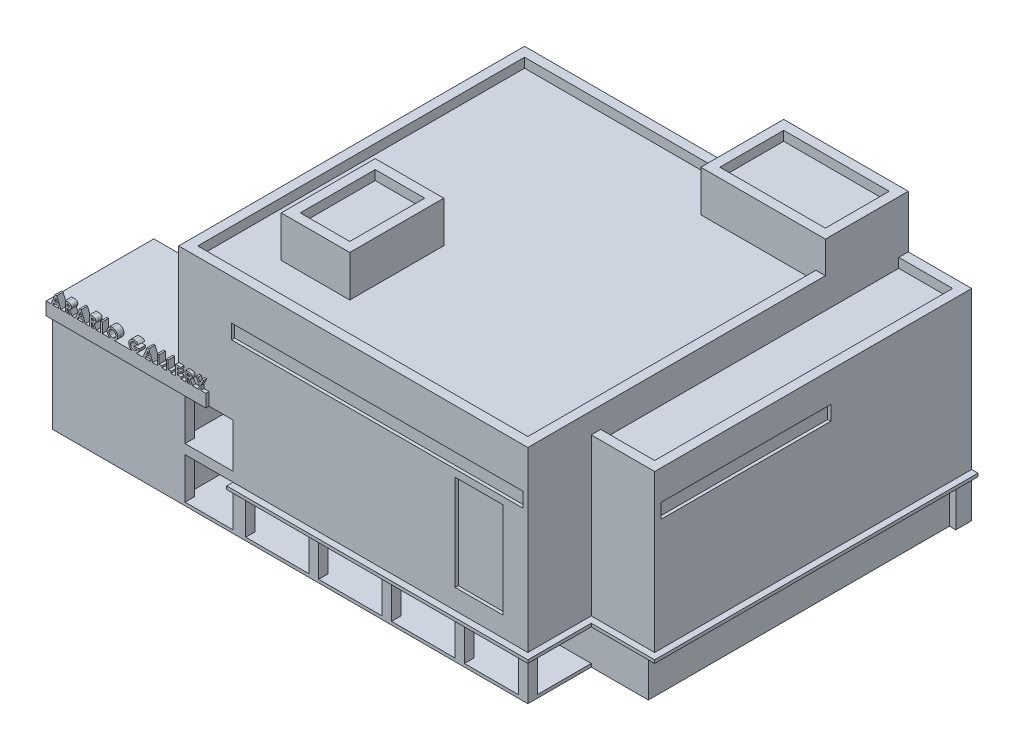
SolidWorks part; units mm, degrees
ref_plane "Front Plane" through (0, 0, 0) normal (0, 0, 1) x (1, 0, 0)
ref_plane "Top Plane" through (0, 0, 0) normal (0, 1, 0) x (1, 0, 0)
ref_plane "Right Plane" through (0, 0, 0) normal (1, 0, 0) x (0, 0, -1)
sketch "Sketch1" plane through (0, 0, 0) normal (0, 0, 1) x (1, 0, 0)
  line L1 (0, 0) -> (170, 0)
  line L2 (0, 0) -> (0, 70)
  line L3 (0, 70) -> (170, 70)
  line L4 (170, 0) -> (170, 70)
  dimension "D1" = 170
  dimension "D2" = 70
extrude "Boss-Extrude1" add sketch "Sketch1" along normal blind 120
sketch "Sketch2" plane through (0, 0, 120) normal (0, 0, 1) x (1, 0, 0)
  line L0 (0, 70) -> (0, 0) construction
  line L1 (0, 70) -> (39.861, 70)
  line L2 (0, 70) -> (0, 35)
  line L3 (0, 35) -> (39.861, 35)
  line L4 (39.861, 70) -> (39.861, 35)
  point P8 (0, 35)
extrude "Cut-Extrude1" cut sketch "Sketch2" against normal blind 150
sketch "Sketch3" plane through (0, 0, 0) normal (-1, 0, 0) x (0, 0, 1)
  line L0 (0, 35) -> (120, 35) construction
  line L1 (0, 0) -> (88.3399, 0)
  line L2 (0, 0) -> (0, 35)
  line L3 (0, 35) -> (88.3399, 35)
  line L4 (88.3399, 0) -> (88.3399, 35)
extrude "Cut-Extrude2" cut sketch "Sketch3" against normal up to vertex (39.861 mm away) up to point (39.861, 35, 0)
sketch "Sketch4" plane through (170, 0, 0) normal (1, 0, 0) x (0, 0, -1)
  line L0 (0, 0) -> (0, 70) construction
  line L1 (-120, 0) -> (-5, 0)
  line L2 (-120, 0) -> (-120, 13)
  line L3 (-120, 13) -> (-5, 13)
  line L4 (-5, 0) -> (-5, 13)
  dimension "D1" = 5
  dimension "D2" = 13
extrude "Cut-Extrude3" cut sketch "Sketch4" against normal blind 2
sketch "Sketch5" plane through (170, 0, 0) normal (1, 0, 0) x (0, 0, -1)
  line L0 (0, 0) -> (0, 70) construction
  line L1 (-120, 13) -> (0, 13)
  line L2 (-120, 13) -> (-120, 14)
  line L3 (-120, 14) -> (0, 14)
  line L4 (0, 13) -> (0, 14)
  dimension "D1" = 1
extrude "Boss-Extrude2" add sketch "Sketch5" along normal blind 2
sketch "Sketch6" plane through (0, 70, 0) normal (0, 1, 0) x (1, 0, 0)
  line L0 (170, -120) -> (39.861, -120) construction
  line L1 (172, -120) -> (150, -120)
  line L2 (172, -120) -> (172, -100)
  line L3 (172, -100) -> (150, -100)
  line L4 (150, -120) -> (150, -100)
  line L5 (170, -120) -> (170, 0) construction
  dimension "D1" = 22
  dimension "D2" = 20
  dimension "D3" = 2
extrude "Cut-Extrude4" cut sketch "Sketch6" against normal up to vertex (70 mm away) up to point (168, 0, 120)
sketch "Sketch7" plane through (0, 0, 100) normal (0, 0, 1) x (1, 0, 0)
  line L0 (150, 0) -> (150, 70) construction
  line L1 (172, 13) -> (150, 13)
  line L2 (172, 13) -> (172, 14)
  line L3 (172, 14) -> (150, 14)
  line L4 (150, 13) -> (150, 14)
extrude "Boss-Extrude3" add sketch "Sketch7" along normal blind 2
sketch "Sketch8" plane through (150, 0, 0) normal (1, 0, 0) x (0, 0, -1)
  line L0 (-120, 0) -> (-120, 70) construction
  line L1 (-102, 13) -> (-120, 13)
  line L2 (-102, 13) -> (-102, 14)
  line L3 (-102, 14) -> (-120, 14)
  line L4 (-120, 13) -> (-120, 14)
  dimension "D1" = 1
extrude "Boss-Extrude4" add sketch "Sketch8" along normal blind 2
sketch "Sketch9" plane through (0, 0, 120) normal (0, 0, 1) x (1, 0, 0)
  line L0 (39.861, 35) -> (39.861, 70) construction
  line L1 (152, 14) -> (39.861, 14)
  line L2 (152, 14) -> (152, 13)
  line L3 (152, 13) -> (39.861, 13)
  line L4 (39.861, 14) -> (39.861, 13)
  dimension "D1" = 1
extrude "Boss-Extrude5" add sketch "Sketch9" along normal blind 2
sketch "Sketch10" plane through (0, 0, 120) normal (0, 0, 1) x (1, 0, 0)
  line L0 (0, 0) -> (150, 0) construction
  line L1 (147, 0) -> (130, 0)
  line L2 (147, 0) -> (147, 13)
  line L3 (147, 13) -> (130, 13)
  line L4 (130, 0) -> (130, 13)
  line L5 (39.861, 13) -> (150, 13) construction
  line L7 (127, 0) -> (107, 0)
  line L8 (127, 0) -> (127, 13)
  line L9 (127, 13) -> (107, 13)
  line L10 (107, 0) -> (107, 13)
  line L11 (104, 13) -> (84, 13)
  line L12 (104, 13) -> (104, 0)
  line L13 (104, 0) -> (84, 0)
  line L14 (84, 13) -> (84, 0)
  line L15 (57, 0) -> (41.861, 0)
  line L16 (57, 0) -> (57, 14)
  line L17 (57, 14) -> (41.861, 14)
  line L18 (41.861, 0) -> (41.861, 14)
  line L19 (41.861, 31) -> (57, 31)
  line L20 (41.861, 31) -> (41.861, 17)
  line L21 (41.861, 17) -> (57, 17)
  line L22 (57, 31) -> (57, 17)
  line L28 (150, 0) -> (150, 13) construction
  line L33 (61, 13) -> (81, 13)
  line L34 (61, 13) -> (61, 0)
  line L35 (61, 0) -> (81, 0)
  line L36 (81, 13) -> (81, 0)
  line L37 (39.861, 35) -> (39.861, 70) construction
  dimension "D1" = 3
  dimension "D2" = 3
  dimension "D3" = 3
  dimension "D4" = 3
  dimension "D5" = 4
  dimension "D6" = 20
  dimension "D7" = 17
  dimension "D8" = 20
  dimension "D9" = 20
  dimension "D10" = 3
  dimension "D11" = 2
  dimension "D12" = 2
extrude "Cut-Extrude7" cut sketch "Sketch10" against normal blind 20 and the other way blind 10
sketch "Sketch12" plane through (150, 0, 0) normal (1, 0, 0) x (0, 0, -1)
  line L0 (-120, 0) -> (-120, 13) construction
  line L1 (-100, 13) -> (-117, 13)
  line L2 (-100, 13) -> (-100, 1)
  line L3 (-100, 1) -> (-117, 1)
  line L4 (-117, 13) -> (-117, 1)
  line L5 (-100, 0) -> (-120, 0) construction
  dimension "D1" = 3
  dimension "D2" = 1
extrude "Cut-Extrude9" cut sketch "Sketch12" against normal blind 109
sketch "Sketch13" plane through (150, 0, 0) normal (1, 0, 0) x (0, 0, -1)
  line L0 (-120, 0) -> (-120, 13) construction
  line L1 (-120, 1) -> (-100, 1)
  line L2 (-120, 1) -> (-120, 0)
  line L3 (-120, 0) -> (-100, 0)
  line L4 (-100, 1) -> (-100, 0)
extrude "Boss-Extrude6" add sketch "Sketch13" against normal blind 108.7
sketch "Sketch14" plane through (41.861, 0, 0) normal (1, 0, 0) x (0, 0, -1)
  line L1 (-120, 13) -> (-122, 13)
  line L2 (-120, 13) -> (-120, 14)
  line L3 (-120, 14) -> (-122, 14)
  line L4 (-122, 13) -> (-122, 14)
extrude "Cut-Extrude10" cut sketch "Sketch14" against normal blind 4.7
sketch "Sketch15" plane through (0, 0, 100) normal (0, 0, 1) x (1, 0, 0)
  line L1 (41.861, 31) -> (57, 31)
  line L2 (41.861, 31) -> (41.861, 17)
  line L3 (41.861, 17) -> (57, 17)
  line L4 (57, 31) -> (57, 17)
  line L5 (41.861, 14) -> (57, 14)
  line L6 (41.861, 14) -> (41.861, 1)
  line L7 (41.861, 1) -> (57, 1)
  line L8 (57, 14) -> (57, 1)
extrude "Cut-Extrude11" cut sketch "Sketch15" against normal blind 69.7
sketch "Sketch16" plane through (39.861, 0, 0) normal (-1, 0, 0) x (0, 0, 1)
  line L0 (30.3, 31) -> (117, 31)
  line L1 (30.3, 31) -> (30.3, 17)
  line L2 (30.3, 17) -> (117, 17)
  line L3 (117, 31) -> (117, 17)
  line L4 (30.3, 14) -> (117, 14)
  line L5 (30.3, 14) -> (30.3, 1)
  line L6 (30.3, 1) -> (117, 1)
  line L7 (117, 14) -> (117, 1)
  line L8 (0, 0) -> (88.3399, 0) construction
  line L9 (120, 35) -> (120, 70) construction
  line L10 (120, 35) -> (120, 0) construction
  line L11 (30.3, 31) -> (30.3, 17) construction
  line L12 (30.3, 14) -> (30.3, 1) construction
  line L13 (42, 31) -> (42, 17)
  line L14 (45, 31) -> (45, 17)
  line L15 (67, 31) -> (67, 17)
  line L16 (70, 31) -> (70, 17)
  line L17 (92, 31) -> (92, 17)
  line L18 (95, 31) -> (95, 17)
  line L19 (42, 14) -> (42, 1)
  line L20 (45, 14) -> (45, 1)
  line L21 (67, 14) -> (67, 1)
  line L22 (70, 14) -> (70, 1)
  line L23 (92, 14) -> (92, 1)
  line L24 (95, 14) -> (95, 1)
  line M17 (88.3399, 0) -> (88.3399, 35)
  dimension "D1" = 1
  dimension "D2" = 14
  dimension "D3" = 13
  dimension "D4" = 3
  dimension "D5" = 3
  dimension "D6" = 3
  dimension "D7" = 3
  dimension "D8" = 3
  dimension "D9" = 3
  dimension "D10" = 22
  dimension "D11" = 22
  dimension "D12" = 22
extrude "Cut-Extrude12" cut sketch "Sketch16" against normal blind 5 contours L13 L0 L1 L2 | L15 L0 L14 L2 | L0 L16 L2 M17 | L17 L0 L2 M17 | L0 L18 L2 L3 | L4 L24 L6 L7 | L4 L22 L6 M17 | L23 L4 L6 M17 | L21 L4 L20 L6 | L19 L4 L5 L6 region at (39.861, 7.5, 90.17) region at (39.861, 7.5, 79.17) region at (39.861, 24, 36.15) region at (39.861, 24, 56) region at (39.861, 24, 79.17) region at (39.861, 24, 90.17) region at (39.861, 24, 106) region at (39.861, 7.5, 56) region at (39.861, 7.5, 106) region at (39.861, 7.5, 36.15)
sketch "Sketch18" plane through (0, 0, 120) normal (0, 0, 1) x (1, 0, 0)
  line L0 (150, 14) -> (150, 70) construction
  line L1 (148.5, 57.2866) -> (56.5, 57.2866)
  line L2 (148.5, 57.2866) -> (148.5, 52.6644)
  line L3 (148.5, 52.6644) -> (56.5, 52.6644)
  line L4 (56.5, 57.2866) -> (56.5, 52.6644)
  line L6 (127.0747, 50.4218) -> (142.2011, 50.4218)
  line L7 (127.0747, 50.4218) -> (127.0747, 20.3005)
  line L8 (127.0747, 20.3005) -> (142.2011, 20.3005)
  line L9 (142.2011, 50.4218) -> (142.2011, 20.3005)
  dimension "D1" = 1.5
  dimension "D2" = 92
extrude "Cut-Extrude13" cut sketch "Sketch18" against normal blind 1
sketch "Sketch19" plane through (0, 0, 120) normal (0, 0, 1) x (1, 0, 0)
  line L0 (57, 31) -> (41.861, 31) construction
  line L1 (49.4305, 31) -> (-1, 31)
  line L2 (49.4305, 31) -> (49.4305, 35)
  line L3 (49.4305, 35) -> (-1, 35)
  line L4 (-1, 31) -> (-1, 35)
  line L5 (0, 35) -> (0, 0) construction
  dimension "D1" = 1
extrude "Boss-Extrude7" add sketch "Sketch19" along normal blind 1 and the other way blind 33
sketch "Sketch20" plane through (0, 0, 121) normal (0, 0, 1) x (1, 0, 0)
  text T0 "<b>ARARIO GALLERY</b>" font "Century Gothic" height in points 12
extrude "Boss-Extrude8" add sketch "Sketch20" against normal blind 2
sketch "Sketch21" plane through (170, 0, 0) normal (1, 0, 0) x (0, 0, -1)
  line L1 (-97.9388, 54) -> (-44.4409, 54)
  line L2 (-97.9388, 54) -> (-97.9388, 49.3778)
  line L3 (-97.9388, 49.3778) -> (-44.4409, 49.3778)
  line L4 (-44.4409, 54) -> (-44.4409, 49.3778)
  line L7 (-100, 70) -> (0, 70) construction
  dimension "D1" = 16
  dimension "D2" = 4.6222
extrude "Cut-Extrude14" cut sketch "Sketch21" against normal blind 1
sketch "Sketch22" plane through (0, 70, 0) normal (0, 1, 0) x (1, 0, 0)
  line L0 (57, -120) -> (57, -30.3) construction
  line L1 (57, -75.15) -> (78.6247, -75.15)
  line L2 (57, -75.15) -> (57, -104.8013)
  line L3 (57, -104.8013) -> (78.6247, -104.8013)
  line L4 (78.6247, -75.15) -> (78.6247, -104.8013)
  line L6 (110.7023, 0) -> (150, 0)
  line L7 (110.7023, 0) -> (110.7023, -26.1456)
  line L8 (110.7023, -26.1456) -> (150, -26.1456)
  line L9 (150, 0) -> (150, -26.1456)
  line L10 (170, 0) -> (39.861, 0) construction
  line L13 (150, -100) -> (150, -120) construction
extrude "Boss-Extrude9" add sketch "Sketch22" along normal blind 10 and the other way up to surface (70 mm away) other way up to face at (105.5722, 0, 62.668)
sketch "Sketch23" plane through (0, 70, 0) normal (0, 1, 0) x (1, 0, 0)
  line L0 (39.861, 0) -> (39.861, -120) construction
  line L1 (110.7023, 0) -> (39.861, 0)
  line L2 (110.7023, 0) -> (110.7023, -10.9097)
  line L3 (110.7023, -10.9097) -> (39.861, -10.9097)
  line L4 (39.861, 0) -> (39.861, -10.9097)
extrude "Cut-Extrude15" cut sketch "Sketch23" against normal up to vertex (70 mm away) up to point (39.861, 0, 0)
sketch "Sketch24" plane through (0, 70, 0) normal (0, 1, 0) x (1, 0, 0)
  line L0 (57, -75.15) -> (57, -104.8013) construction
  line L1 (42.861, -13.9097) -> (110.7023, -13.9097)
  line L2 (42.861, -13.9097) -> (42.861, -75.15)
  line L3 (57, -75.15) -> (78.6247, -75.15)
  line L4 (110.7023, -13.9097) -> (110.7023, -26.1456)
  line L5 (150, -3) -> (147, -3)
  line L6 (150, -3) -> (150, -26.1456)
  line L8 (147, -3) -> (147, -97)
  line L9 (110.7023, -26.1456) -> (150, -26.1456)
  line L11 (97.1489, -117) -> (147, -117)
  line L12 (147, -97) -> (147, -117)
  line L14 (78.6247, -75.15) -> (78.6247, -104.8013)
  line L15 (78.6247, -117) -> (103.4716, -117)
  line L18 (42.861, -67.473) -> (42.861, -117)
  line L19 (42.861, -117) -> (57, -117)
  line L20 (57, -75.15) -> (57, -104.8013)
  line L21 (85.8039, -117) -> (57, -117)
  line L23 (78.6247, -104.8013) -> (57, -104.8013)
  line L25 (39.861, -10.9097) -> (110.7023, -10.9097) construction
  line L26 (39.861, -10.9097) -> (39.861, -120) construction
  line L27 (150, -120) -> (39.861, -120) construction
  line L28 (150, -100) -> (150, -120) construction
  line L30 (170, 0) -> (150, 0) construction
  line L31 (150, -26.1456) -> (150, 0) construction
  line L32 (110.7023, 0) -> (110.7023, -26.1456) construction
  line L33 (110.7023, -26.1456) -> (150, -26.1456) construction
  line L34 (57, -104.8013) -> (78.6247, -104.8013) construction
  line L35 (78.6247, -104.8013) -> (78.6247, -75.15) construction
  line L36 (78.6247, -75.15) -> (57, -75.15) construction
  line M22 (78.6247, -104.8013) -> (57, -104.8013)
  line M23 (57, -104.8013) -> (57, -75.15)
  line M24 (57, -75.15) -> (78.6247, -75.15)
  line M25 (78.6247, -75.15) -> (78.6247, -104.8013)
  line M26 (110.7023, -26.1456) -> (110.7023, -10.9097)
  line M34 (150, 0) -> (150, -26.1456)
  line M35 (150, -26.1456) -> (110.7023, -26.1456)
  dimension "D1" = 3
  dimension "D2" = 3
  dimension "D3" = 3
  dimension "D4" = 3
  dimension "D5" = 3
  dimension "D7" = 3
extrude "Cut-Extrude16" cut sketch "Sketch24" against normal blind 3 contours L21 L15 L11 L12 L8 L5 L1 L2 L18 L19 M34 M35 M26 M25 M22 M23 M24 region at (95.1712, 70, 65.9163)
sketch "Sketch25" plane through (0, 0, 100) normal (0, 0, 1) x (1, 0, 0)
  line L0 (170, 70) -> (170, 14) construction
  line L1 (150, 70) -> (170, 70)
  line L2 (150, 70) -> (150, 63.4447)
  line L3 (150, 63.4447) -> (170, 63.4447)
  line L4 (170, 70) -> (170, 63.4447)
extrude "Cut-Extrude17" cut sketch "Sketch25" against normal up to vertex (100 mm away) up to point (170, 14, 0)
sketch "Sketch26" plane through (0, 63.4447, 0) normal (0, 1, 0) x (1, 0, 0)
  line L0 (150, 0) -> (170, 0) construction
  line L1 (150, -3) -> (167, -3)
  line L2 (150, -3) -> (150, -97)
  line L3 (150, -97) -> (167, -97)
  line L4 (167, -3) -> (167, -97)
  line L6 (170, 0) -> (170, -100) construction
  line L8 (150, -100) -> (170, -100) construction
  line L9 (150, -26.1456) -> (150, -120) construction
  dimension "D1" = 3
  dimension "D3" = 3
  dimension "D4" = 3
extrude "Cut-Extrude18" cut sketch "Sketch26" against normal blind 3
sketch "Sketch27" plane through (0, 80, 0) normal (0, 1, 0) x (1, 0, 0)
  line L0 (110.7023, -26.1456) -> (150, -26.1456) construction
  line L1 (113.7023, -3) -> (147, -3)
  line L2 (113.7023, -3) -> (113.7023, -23.1456)
  line L3 (113.7023, -23.1456) -> (147, -23.1456)
  line L4 (147, -3) -> (147, -23.1456)
  line L5 (60, -78.15) -> (75.6247, -78.15)
  line L6 (60, -78.15) -> (60, -101.8013)
  line L7 (60, -101.8013) -> (75.6247, -101.8013)
  line L8 (75.6247, -78.15) -> (75.6247, -101.8013)
  line L9 (150, 0) -> (110.7023, 0) construction
  line L10 (110.7023, 0) -> (110.7023, -26.1456) construction
  line L11 (150, -26.1456) -> (150, 0) construction
  line L12 (78.6247, -75.15) -> (57, -75.15) construction
  line L13 (57, -104.8013) -> (78.6247, -104.8013) construction
  line L14 (78.6247, -104.8013) -> (78.6247, -75.15) construction
  line L15 (57, -75.15) -> (57, -104.8013) construction
  dimension "D1" = 3
  dimension "D2" = 3
  dimension "D3" = 3
  dimension "D4" = 3
  dimension "D5" = 3
  dimension "D6" = 3
  dimension "D7" = 3
  dimension "D8" = 3
extrude "Cut-Extrude19" cut sketch "Sketch27" against normal blind 3
sketch "Sketch28" plane through (0, 0, 0) normal (0, 0, -1) x (-1, 0, 0)
  line L0 (-169, 49.3778) -> (-170, 49.3778) construction
  line L1 (-165, 54.0068) -> (-154, 54.0068)
  line L2 (-165, 54.0068) -> (-165, 49.3778)
  line L3 (-165, 49.3778) -> (-154, 49.3778)
  line L4 (-154, 54.0068) -> (-154, 49.3778)
  line L5 (-150, 63.4447) -> (-150, 80) construction
  line L6 (-170, 14) -> (-170, 63.4447) construction
  line L7 (-165, 43.3778) -> (-154, 43.3778)
  line L8 (-165, 43.3778) -> (-165, 38.7489)
  line L9 (-165, 38.7489) -> (-154, 38.7489)
  line L10 (-154, 43.3778) -> (-154, 38.7489)
  line L11 (-165, 32.7489) -> (-154, 32.7489)
  line L12 (-165, 32.7489) -> (-165, 28.1199)
  line L13 (-165, 28.1199) -> (-154, 28.1199)
  line L14 (-154, 32.7489) -> (-154, 28.1199)
  line L15 (-165, 22.1199) -> (-154, 22.1199)
  line L16 (-165, 22.1199) -> (-165, 17.491)
  line L17 (-165, 17.491) -> (-154, 17.491)
  line L18 (-154, 22.1199) -> (-154, 17.491)
  line L20 (-165, 11.491) -> (-154, 11.491)
  line L21 (-165, 11.491) -> (-165, 6.8621)
  line L22 (-165, 6.8621) -> (-154, 6.8621)
  line L23 (-154, 11.491) -> (-154, 6.8621)
  dimension "D1" = 4
  dimension "D2" = 5
  dimension "D3" = 4.6289
  dimension "D4" = 4.6289
  dimension "D5" = 4.6289
  dimension "D6" = 4.6289
  dimension "D7" = 6
  dimension "D8" = 6
  dimension "D9" = 6
  dimension "D10" = 4.6289
  dimension "D11" = 6
extrude "Cut-Extrude20" cut sketch "Sketch28" against normal blind 1
sketch "Sketch29" plane through (0, 0, 10.9097) normal (0, 0, -1) x (-1, 0, 0)
  line L0 (-154, 54.0068) -> (-165, 54.0068) construction
  line L1 (-107.7023, 54.0068) -> (-42.861, 54.0068)
  line L2 (-107.7023, 54.0068) -> (-107.7023, 49.3778)
  line L3 (-107.7023, 49.3778) -> (-42.861, 49.3778)
  line L4 (-42.861, 54.0068) -> (-42.861, 49.3778)
  line L5 (-165, 49.3778) -> (-154, 49.3778) construction
  line L6 (-39.861, 0) -> (-39.861, 70) construction
  line L7 (-110.7023, 0) -> (-110.7023, 80) construction
  dimension "D1" = 3
  dimension "D2" = 3
extrude "Cut-Extrude21" cut sketch "Sketch29" against normal blind 1
sketch "Sketch30" plane through (0, 0, 0) normal (0, -1, 0) x (1, 0, 0)
  line L0 (60, 78.15) -> (60, 101.8013) construction
  line L1 (60, 97) -> (165, 97)
  line L2 (60, 97) -> (60, 13.9097)
  line L3 (60, 13.9097) -> (165, 13.9097)
  line L4 (165, 97) -> (165, 13.9097)
  line L5 (0, 120) -> (150, 120) construction
  line L6 (3, 117) -> (36.861, 117)
  line L7 (3, 117) -> (3, 91.3399)
  line L8 (3, 91.3399) -> (36.861, 91.3399)
  line L9 (36.861, 117) -> (36.861, 91.3399)
  line L10 (42.861, 26.2082) -> (61, 26.2082)
  line L11 (42.861, 26.2082) -> (42.861, 13.9097)
  line L12 (42.861, 13.9097) -> (61, 13.9097)
  line L13 (61, 26.2082) -> (61, 13.9097)
  line L14 (0, 120) -> (0, 88.3399) construction
  line L15 (39.861, 88.3399) -> (0, 88.3399) construction
  line L16 (39.861, 95) -> (39.861, 117) construction
  line L17 (78.6247, 100) -> (150, 100) construction
  line L18 (168, 100) -> (168, 5) construction
  line L19 (39.861, 10.9097) -> (110.7023, 10.9097) construction
  line L20 (39.861, 10.9097) -> (39.861, 88.3399) construction
  line L22 (165, 13.9097) -> (113.7023, 13.9097)
  line L23 (165, 13.9097) -> (165, 3)
  line L24 (165, 3) -> (113.7023, 3)
  line L25 (113.7023, 13.9097) -> (113.7023, 3)
  dimension "D1" = 3
  dimension "D2" = 3
  dimension "D3" = 3
  dimension "D4" = 3
  dimension "D5" = 3
  dimension "D6" = 3
  dimension "D7" = 3
  dimension "D8" = 3
extrude "Cut-Extrude22" cut sketch "Sketch30" against normal offset from surface (32 mm away) 3 contours L9 L6 L7 L8 | L11 L12 L2 L10 | L3 L25 L24 L23 | L3 L2 L1 L4 region at (51.4305, 0, 20.0589) region at (139.3512, 0, 8.4548) region at (19.9305, 0, 104.17) up to face at (18.2548, 35, 119.0303)
sketch "Sketch31" plane through (78.6247, 0, 0) normal (1, 0, 0) x (0, 0, -1)
  line L1 (-100, 13) -> (-104.8013, 13)
  line L2 (-100, 13) -> (-100, 1)
  line L3 (-100, 1) -> (-104.8013, 1)
  line L4 (-104.8013, 13) -> (-104.8013, 1)
extrude "Cut-Extrude23" cut sketch "Sketch31" against normal up to vertex (21.6247 mm away) up to point (57, 13, 104.8013)
sketch "Sketch32" plane through (0, 32, 0) normal (0, -1, 0) x (1, 0, 0)
  line L0 (60, 97) -> (60, 26.2082)
  line L1 (60, 26.2082) -> (42.861, 26.2082)
  line L2 (42.861, 26.2082) -> (42.861, 13.9097)
  line L3 (42.861, 13.9097) -> (113.7023, 13.9097)
  line L4 (113.7023, 13.9097) -> (113.7023, 3)
  line L5 (113.7023, 3) -> (165, 3)
  line L6 (165, 3) -> (165, 97)
  line L7 (165, 97) -> (60, 97)
extrude "Cut-Extrude24" cut sketch "Sketch32" against normal offset from surface (25.4447 mm away) 3 up to face at (158.5, 60.4447, 50)
sketch "Sketch33" plane through (0, 57.4447, 0) normal (0, -1, 0) x (1, 0, 0)
  line L0 (60, 97) -> (165, 97) construction
  line L1 (147, 97) -> (60, 97)
  line L2 (147, 97) -> (147, 13.9097)
  line L3 (147, 13.9097) -> (60, 13.9097)
  line L4 (60, 97) -> (60, 13.9097)
  line L5 (147, 26.1456) -> (147, 117) construction
  line L6 (42.861, 13.9097) -> (113.7023, 13.9097) construction
  line L8 (60, 26.2082) -> (42.861, 26.2082)
  line L9 (60, 26.2082) -> (60, 13.9097)
  line L10 (60, 13.9097) -> (42.861, 13.9097)
  line L11 (42.861, 26.2082) -> (42.861, 13.9097)
  line L12 (147, 13.9097) -> (113.7023, 13.9097)
  line L13 (147, 13.9097) -> (147, 3)
  line L14 (147, 3) -> (113.7023, 3)
  line L15 (113.7023, 13.9097) -> (113.7023, 3)
  line M1 (165, 97) -> (60, 97)
  line M2 (60, 97) -> (60, 26.2082)
  line M5 (42.861, 13.9097) -> (113.7023, 13.9097)
extrude "Cut-Extrude25" cut sketch "Sketch33" against normal blind 3 contours L4 L3 L2 M2 M5 M1 region at (103.5, 57.4447, 55.4548)
sketch "Sketch34" plane through (0, 60.4447, 0) normal (0, -1, 0) x (1, 0, 0)
  line L1 (75.6247, 78.15) -> (60, 78.15)
  line L2 (75.6247, 78.15) -> (75.6247, 101.8013)
  line L3 (75.6247, 101.8013) -> (60, 101.8013)
  line L4 (60, 78.15) -> (60, 101.8013)
extrude "Cut-Extrude26" cut sketch "Sketch34" against normal offset from surface (13.5553 mm away) 3 up to face at (67.8123, 77, 89.9757)
sketch "Sketch35" plane through (60, 0, 0) normal (1, 0, 0) x (0, 0, -1)
  line L0 (-97, 60.4447) -> (-97, 0) construction
  line L1 (-13.9097, 60.4447) -> (-97, 60.4447)
  line L2 (-13.9097, 60.4447) -> (-13.9097, 34)
  line L3 (-13.9097, 34) -> (-97, 34)
  line L4 (-97, 60.4447) -> (-97, 34)
  line L5 (-120, 31) -> (-30.3, 31) construction
  dimension "D1" = 3
extrude "Cut-Extrude27" cut sketch "Sketch35" against normal offset from surface (17.139 mm away) 3 up to face at (39.861, 24, 76.3699)
sketch "Sketch36" plane through (0, 0, 97) normal (0, 0, -1) x (-1, 0, 0)
  line L0 (-60, 34) -> (-60, 0) construction
  line L1 (-147, 60.4447) -> (-60, 60.4447)
  line L2 (-147, 60.4447) -> (-147, 16)
  line L3 (-147, 16) -> (-60, 16)
  line L4 (-60, 34) -> (-60, 16)
  line L5 (-57, 13) -> (-168, 13) construction
  line L6 (-60, 60.4447) -> (-42.861, 60.4447)
  line L8 (-60, 34) -> (-42.861, 34)
  line L9 (-42.861, 60.4447) -> (-42.861, 34)
  dimension "D1" = 3
extrude "Cut-Extrude28" cut sketch "Sketch36" against normal offset from surface (20 mm away) 3 up to face at (134.6379, 35.3612, 120)
